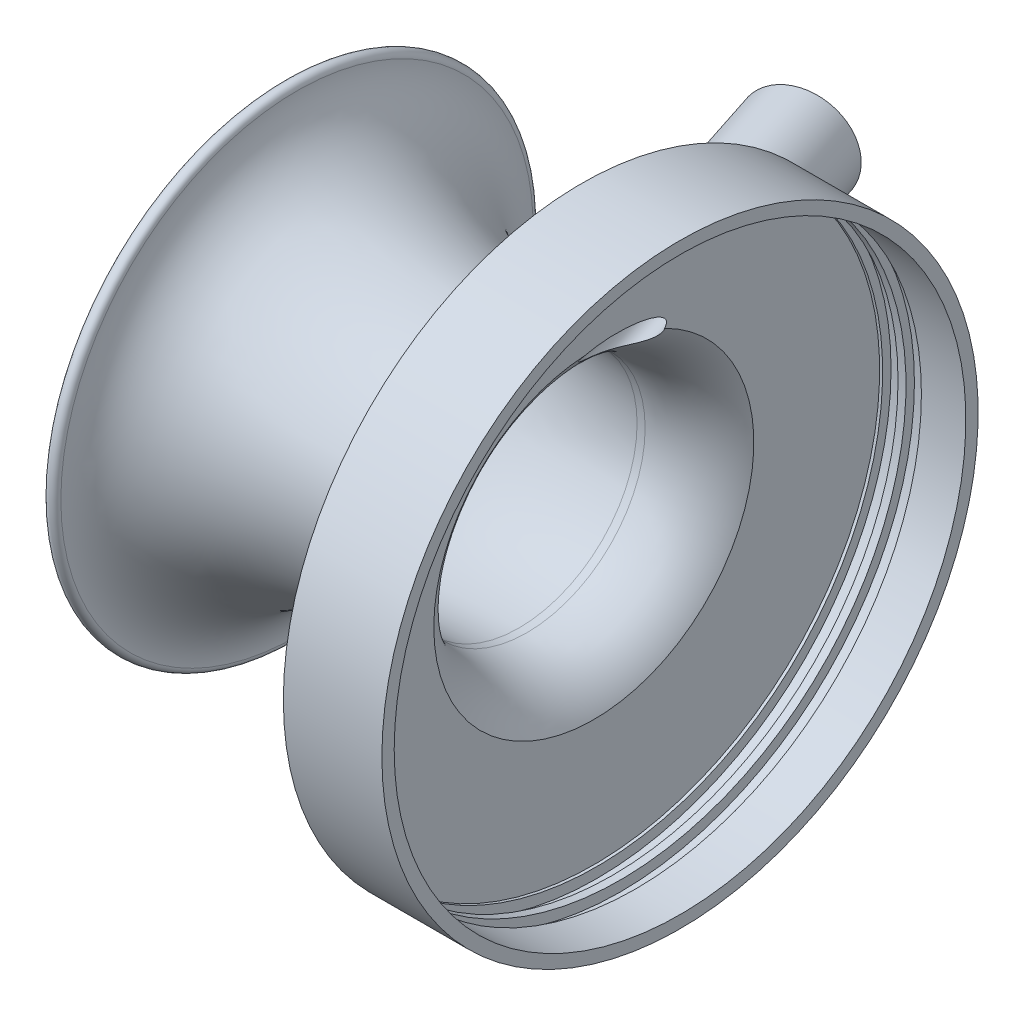
SolidWorks part; units mm, degrees
material "PVC 0.007 Plasticized"
ref_plane "Front Plane" through (0, 0, 0) normal (0, 0, 1) x (1, 0, 0)
ref_plane "Top Plane" through (0, 0, 0) normal (0, 1, 0) x (1, 0, 0)
ref_plane "Right Plane" through (0, 0, 0) normal (1, 0, 0) x (0, 0, -1)
sketch "Sketch1" plane through (0, 0, 0) normal (0, 0, 1) x (1, 0, 0)
  line L0 (-17.78, 33.4033) -> (-17.78, 59.3503)
  line L1 (-34.3222, 33.4033) -> (-9.5791, 33.4033) construction
  line L3 (-34.3222, 0.4033) -> (53.9483, 0.4033) construction
  line L11 (-33.2131, 24.7619) -> (-31.5799, 24.7915)
  line L12 (-17.78, 59.3503) -> (0, 59.3503)
  line L13 (-33.2365, 27.3019) -> (-31.68, 27.3301)
  line L14 (-20.32, 34.0999) -> (-20.32, 61.8903)
  line L15 (-20.32, 61.8903) -> (0, 61.8903)
  line L16 (0, 61.8903) -> (0, 59.3503)
  circle A4 centre (-32.5832, 41.7619) radius 17 construction
  arc A5 (-17.78, 33.4033) -> (-31.5799, 24.7915) centre (-32.5832, 41.7619) cw
  arc A6 (-20.32, 34.0999) -> (-31.68, 27.3301) centre (-32.5832, 41.7619) cw
  arc A7 (-81.5276, 49.1004) -> (-78.9876, 49.1015) centre (-80.2576, 49.101) cw
  ellipse E0 centre (-33.2232, 49.1205) end of major axis (-81.5276, 49.1004) minor radius 24.3586 (-81.5276, 49.1004) -> (-33.2131, 24.7619) ccw
  ellipse E1 centre (-33.2232, 49.1205) end of major axis (-81.5276, 49.1004) minor radius 24.3586 construction
  spline S0 degree 1 poles (-78.9876, 49.1015) (-33.2365, 27.3019) knots 0 0 1 1 construction
  spline S1 degree 3 poles (-78.9876, 49.1015) (-78.9874, 48.4651) (-78.8643, 47.2068) (-78.1154, 44.6473) (-76.1728, 41.3828) (-72.1247, 37.5428) (-66.4667, 34.0595) (-59.4331, 31.146) (-51.3175, 28.9592) (-42.4745, 27.6059) (-36.296, 27.3013) (-33.2365, 27.3019) knots 3.141593 3.141593 3.141593 3.141593 3.239738 3.337883 3.534173 3.730463 3.926753 4.123043 4.319333 4.515623 4.711913 4.711913 4.711913 4.711913
  dimension "D3" = 24.3586
  dimension "D1" = 33.0001
  dimension "D2" = 15.4432
  dimension "D4" = 48.3044
  dimension "D5" = 58.947
  dimension "D10" = 34
  dimension "D11" = 17
  dimension "D12" = 31.5799
  dimension "D9" = 1.27
  dimension "D6" = 17.78
  dimension "D8" = 24.3586
  dimension "D7" = 2.54
  dimension "D13" = 31.68
  dimension "D14" = 34.3222
  dimension "D15" = 0.4033
revolve "Revolve1" add sketch "Sketch1" angle 360 about L3
ref_axis "Axis1" through (0, 65.659, 0) along (0, -1, 0)
ref_plane "Plane1" through (0, 0, 0) normal (-0.309, 0, -0.9511) x (0, -1, 0)
ref_plane "Plane2" through (-13.3434, 0, -41.0666) normal (-0.309, 0, -0.9511) x (0, -1, 0)
sketch "Sketch2" plane through (-13.3434, 0, -41.0666) normal (-0.309, 0, -0.9511) x (0, -1, 0)
  line L0 (-33.0001, 18.6255) -> (-26.9006, 18.6255) construction
  circle A0 centre (-30.8893, 15.4505) radius 3.175
  circle A1 centre (-30.8893, 15.4505) radius 10.16
  circle A2 centre (-30.8893, 15.4505) radius 5.5562
  ellipse E0 centre (0, 18.6255) end of major axis (-33.0001, 18.6255) minor radius 9.0224 construction
  dimension "D1" = 6.35
  dimension "D2" = 20.32
  dimension "D3" = 11.1125
  dimension "D4" = 0
extrude "Boss-Extrude1" add sketch "Sketch2" against normal up to next separate body contours A2 A0 region at (-28.0376, 36.2884, -36.2922)
extrude "Cut-Extrude1" cut sketch "Sketch2<3>" along direction (-0.309, 0, -0.9511) on the side against the normal blind 40.64 and the other way through all contours A0 region at (-28.0376, 30.8893, -36.2922)
sketch "Sketch2<3>" plane through (-13.3434, 0, -41.0666) normal (-0.309, 0, -0.9511) x (0, -1, 0) same geometry as "Sketch2"
extrude "Boss-Extrude3" add sketch "Sketch2<4>" against normal blind 1.016 and the other way blind 25.4 contours A1 A2 region at (-28.0376, 40.7619, -36.2922)
sketch "Sketch2<4>" plane through (-13.3434, 0, -41.0666) normal (-0.309, 0, -0.9511) x (0, -1, 0) same geometry as "Sketch2"
sketch "Sketch5" plane through (0, 0, 0) normal (0, 0, 1) x (1, 0, 0)
  line L0 (-13.9854, 60.6838) -> (-17.1604, 60.6838)
  line L1 (-13.9854, 60.6838) -> (-13.9854, 59.0963)
  line L2 (-17.1604, 60.6838) -> (-17.1604, 59.0963)
  line L4 (0, 0) -> (-88.0301, 0) construction
  line L5 (-17.1604, 59.0963) -> (-17.1604, 57.8263)
  line L7 (-13.9854, 57.8263) -> (-13.9854, 59.0963)
  line L14 (-17.1604, 57.8263) -> (-13.9854, 57.8263)
  line L15 (-9.1671, 60.6838) -> (-12.3421, 60.6838)
  line L16 (-9.1671, 60.6838) -> (-9.1671, 59.0963)
  line L17 (-12.3421, 60.6838) -> (-12.3421, 59.0963)
  line L18 (-12.3421, 59.0963) -> (-12.3421, 57.8263)
  line L19 (-9.1671, 57.8263) -> (-9.1671, 59.0963)
  line L20 (-12.3421, 57.8263) -> (-9.1671, 57.8263)
  line L21 (-20.32, 61.8903) -> (-20.32, -61.0838) construction
  line L22 (-20.32, 61.8903) -> (-20.32, -61.0838)
  dimension "D1" = 1.5875
  dimension "D2" = 59.0963
  dimension "D3" = 3.175
  dimension "D4" = 0
  dimension "D5" = 13.9854
  dimension "D6" = 1.27
  dimension "D8" = 1.5875
  dimension "D9" = 3.175
  dimension "D11" = 9.1671
revolve "Cut-Revolve2" cut sketch "Sketch5" angle 360 about L4 region at (-15.5729, 59.2551, 0) region at (-10.7546, 59.2551, 0)
